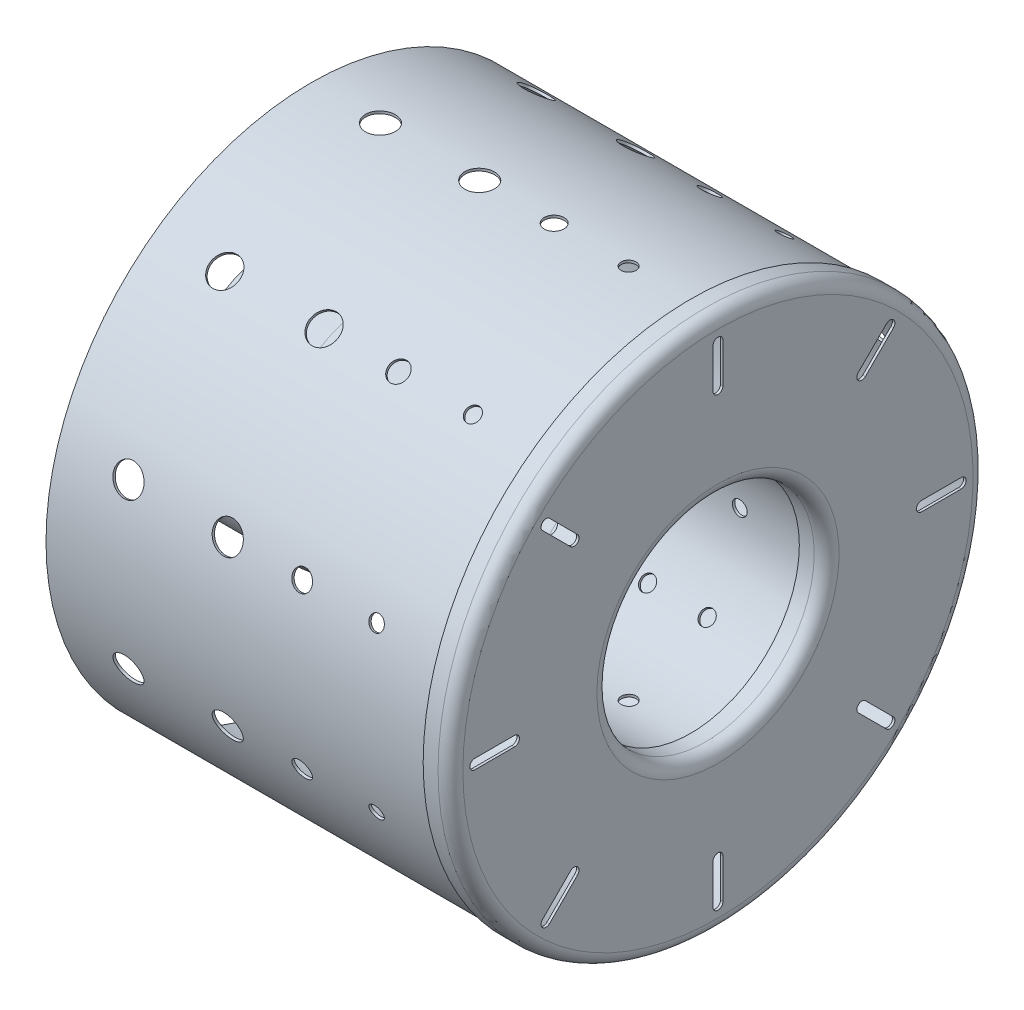
SolidWorks part; units mm, degrees
ref_plane "Ön Düzlem" through (0, 0, 0) normal (0, 0, 1) x (1, 0, 0)
ref_plane "Üst Düzlem" through (0, 0, 0) normal (0, 1, 0) x (1, 0, 0)
ref_plane "Sağ Düzlem" through (0, 0, 0) normal (1, 0, 0) x (0, 0, -1)
sketch "Çizim1" plane through (0, 0, 0) normal (0, 0, 1) x (1, 0, 0)
  line L0 (-44.4676, 0) -> (40.5324, 0) construction
  line L1 (-44.4676, 22.4) -> (-24.9966, 22.4)
  line L2 (-23.9705, 22.2191) -> (-17.1304, 19.7295)
  line L3 (-15.3279, 19.6508) -> (-5.4491, 22.2978)
  line L4 (-4.6726, 22.4) -> (40.5324, 22.4)
  line L5 (-44.4676, 22.9) -> (-24.9966, 22.9)
  line L6 (-23.7995, 22.6889) -> (-16.9594, 20.1993)
  line L7 (-15.4573, 20.1337) -> (-5.5785, 22.7807)
  line L8 (-4.6726, 22.9) -> (40.5324, 22.9)
  line L9 (-44.4676, 22.4) -> (-44.4676, 22.9)
  line L10 (40.5324, 22.4) -> (40.5324, 22.9)
  arc A0 (-5.4491, 22.2978) -> (-4.6726, 22.4) centre (-4.6726, 19.4) cw
  arc A1 (-17.1304, 19.7295) -> (-15.3279, 19.6508) centre (-16.1043, 22.5485) ccw
  arc A2 (-24.9966, 22.4) -> (-23.9705, 22.2191) centre (-24.9966, 19.4) cw
  arc A3 (-24.9966, 22.9) -> (-23.7995, 22.6889) centre (-24.9966, 19.4) cw
  arc A4 (-16.9594, 20.1993) -> (-15.4573, 20.1337) centre (-16.1043, 22.5485) ccw
  arc A5 (-5.5785, 22.7807) -> (-4.6726, 22.9) centre (-4.6726, 19.4) cw
  point P10 (-5.0676, 22.4)
  point P15 (-24.4676, 22.4)
  dimension "D8" = 3
  dimension "D1" = 85
  dimension "D2" = 22.4
  dimension "D3" = 20
  dimension "D4" = 45.6
  dimension "D5" = 145
  dimension "D6" = 160
  dimension "D7" = 165
  dimension "D9" = 0.5
revolve "Döndür2" add sketch "Çizim1" angle 360 about L0
ref_plane "Düzlem1" through (0, 22.9, 0) normal (0, 1, 0) x (1, 0, 0)
sketch "Çizim2" plane through (0, 22.9, 0) normal (0, 1, 0) x (1, 0, 0)
  line L0 (-50.3481, 0) -> (59.5012, 0) construction
  line L1 (-44.4676, 22.9) -> (-44.4676, -22.9) construction
  circle A0 centre (-32.4676, 0) radius 2
  circle A1 centre (1.5324, 0) radius 2
  circle A2 centre (13.5324, 0) radius 1.5
  circle A3 centre (25.5324, 0) radius 1.5
  dimension "D1" = 4
  dimension "D3" = 4
  dimension "D4" = 3
  dimension "D5" = 3
  dimension "D2" = 12
  dimension "D6" = 46
  dimension "D7" = 12
  dimension "D8" = 12
extrude "Kes-Ekstrüzyon2" cut sketch "Çizim2" against normal blind 10
pattern_circular "Dairesel Kaplama1" count 8 over 360 about axis through (40.5324, 0, 0) along (-1, 0, 0) of "Kes-Ekstrüzyon2"
sketch "Çizim3" plane through (0, 0, 0) normal (0, 0, 1) x (1, 0, 0)
  line L0 (-53.4944, 0) -> (64.1775, 0) construction
  line L1 (38.0324, 22.4) -> (41.0324, 22.4)
  line L2 (43.0324, 24.4) -> (43.0324, 51.4)
  line L3 (41.0324, 53.4) -> (38.0324, 53.4)
  line L4 (40.5324, -22.9) -> (40.5324, 22.9) construction
  line L5 (38.0324, 21.9) -> (41.0324, 21.9)
  line L6 (43.5324, 24.4) -> (43.5324, 51.4)
  line L7 (41.0324, 53.9) -> (38.0324, 53.9)
  line L8 (38.0324, 53.4) -> (38.0324, 53.9)
  line L9 (38.0324, 21.9) -> (38.0324, 22.4)
  arc A0 (43.0324, 51.4) -> (41.0324, 53.4) centre (41.0324, 51.4) ccw
  arc A1 (41.0324, 22.4) -> (43.0324, 24.4) centre (41.0324, 24.4) ccw
  arc A2 (41.0324, 21.9) -> (43.5324, 24.4) centre (41.0324, 24.4) ccw
  arc A3 (43.5324, 51.4) -> (41.0324, 53.9) centre (41.0324, 51.4) ccw
  point P12 (43.0324, 22.4)
  dimension "D3" = 2
  dimension "D1" = 22.4
  dimension "D2" = 53.4
  dimension "D4" = 3
  dimension "D5" = 3
  dimension "D6" = 2.5
  dimension "D7" = 0.5
revolve "Döndür5" add sketch "Çizim3" angle 360 about L0
ref_plane "Düzlem4" through (4.5081, -12.3858, 0) normal (0.342, -0.9397, 0) x (-0.9397, -0.342, 0)
sketch "Çizim10" plane through (4.5081, -12.3858, 0) normal (0.342, -0.9397, 0) x (-0.9397, -0.342, 0)
  line L0 (67.7625, 0) -> (4.3908, 0) construction
  circle A0 centre (26.3233, 0) radius 3
  dimension "D1" = 6
extrude "Kes-Ekstrüzyon6" cut sketch "Çizim10" against normal blind 4
pattern_circular "Dairesel Kaplama3" count 8 over 360 about axis through (-44.4676, 0, 0) along (-1, 0, 0) of "Kes-Ekstrüzyon6" reverse direction yes
sketch "Çizim11" plane through (0, 0, 0) normal (0, 0, 1) x (1, 0, 0)
  line L0 (-56.7328, 0) -> (73.6757, 0) construction
  line L1 (41.0324, 52.9) -> (-38.4676, 52.9)
  line L2 (41.0324, 53.9) -> (41.0324, -53.9) construction
  line L3 (41.0324, 53.4) -> (-38.4676, 53.4)
  line L4 (-38.4676, 52.9) -> (-38.4676, 53.4)
  line L5 (41.0324, 52.9) -> (41.0324, 53.4)
  dimension "D1" = 0.5
  dimension "D2" = 53.4
  dimension "D3" = 6
revolve "Döndür6" add sketch "Çizim11" angle 360 about L0
ref_plane "Düzlem5" through (0, -53.4, 0) normal (0, -1, 0) x (-1, 0, 0)
sketch "Çizim12" plane through (0, -53.4, 0) normal (0, -1, 0) x (-1, 0, 0)
  line L0 (80.2161, 0) -> (-62.1113, 0) construction
  line L1 (44.4676, -22.9) -> (44.4676, 22.9) construction
  circle A0 centre (-25.5324, 0) radius 1.5
  circle A1 centre (-10.5324, 0) radius 2
  circle A2 centre (4.4676, 0) radius 3
  circle A3 centre (24.4676, 0) radius 3
  dimension "D1" = 6
  dimension "D2" = 6
  dimension "D3" = 4
  dimension "D4" = 3
  dimension "D5" = 20
  dimension "D6" = 20
  dimension "D7" = 15
  dimension "D8" = 15
extrude "Kes-Ekstrüzyon8" cut sketch "Çizim12" against normal blind 4
pattern_circular "Dairesel Kaplama7" count 10 over 360 about axis through (-38.4676, 0, 0) along (-1, 0, 0) of "Kes-Ekstrüzyon8"
sketch "Çizim16" plane through (43.5324, 0, 0) normal (1, 0, 0) x (0, 0, -1)
  line L0 (0, 0) -> (0, 45) construction
  line L1 (0, 49) -> (0, 41) construction
  line L2 (1, 49) -> (1, 41)
  line L3 (-1, 49) -> (-1, 41)
  arc A0 (1, 49) -> (-1, 49) centre (0, 49) ccw
  arc A1 (-1, 41) -> (1, 41) centre (0, 41) ccw
  point P5 (0, 45)
  dimension "D1" = 45
  dimension "D2" = 2
  dimension "D3" = 8
extrude "Kes-Ekstrüzyon9" cut sketch "Çizim16" against normal blind 4
pattern_circular "Dairesel Kaplama9" count 8 over 360 about axis through (43.5324, 0, 0) along (-1, 0, 0) of "Kes-Ekstrüzyon9"
